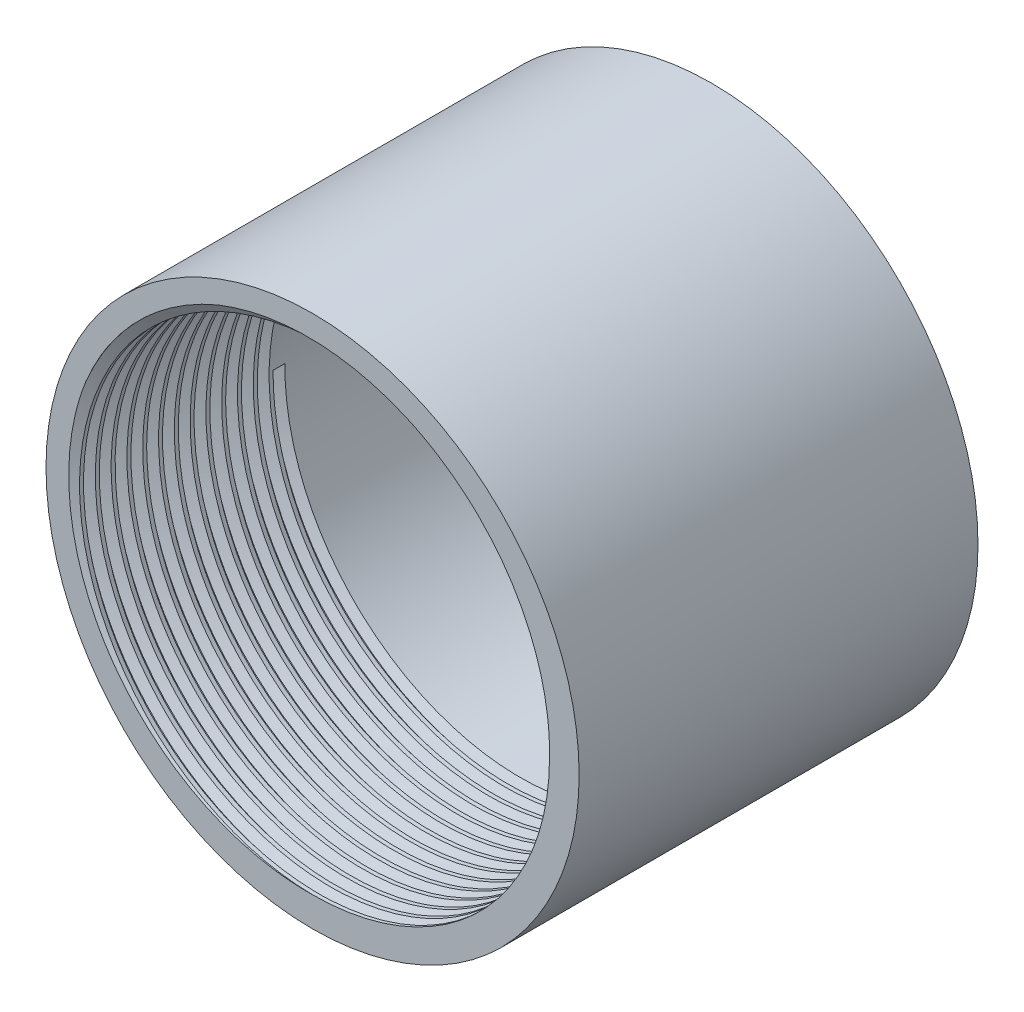
SolidWorks part; units mm, degrees
material "AISI 1035 Acier (SS)"
ref_plane "Plan de face" through (0, 0, 0) normal (0, 0, 1) x (1, 0, 0)
ref_plane "Plan de dessus" through (0, 0, 0) normal (0, 1, 0) x (1, 0, 0)
ref_plane "Plan de droite" through (0, 0, 0) normal (1, 0, 0) x (0, 0, -1)
sketch "Esquisse1" plane through (0, 0, 0) normal (1, 0, 0) x (0, 0, -1)
  line L0 (-10.1, 0) -> (10.1, 0) construction
  line L2 (-10.1, 13.5) -> (10.1, 13.5)
  line L3 (-10.1, 13.5) -> (-10.1, 12)
  line L4 (-10.1, 12) -> (10.1, 12)
  line L5 (10.1, 13.5) -> (10.1, 12)
  dimension "D1" = 20.2
  dimension "D2" = 12
  dimension "D3" = 1.5
revolve "Révolution1" add sketch "Esquisse1" angle 360 about L0
thread "Filetage1" [suppressed] pitch 0.8 start angle 0, offset 2, length 8.5, pitch 0.8, diameter 24
ref_plane "Plan1" through (12, 0, -52.1) normal (0, -1, 0) x (1, 0, 0)
sketch "Profil de filetage1" plane through (12, 0, -52.1) normal (0, -1, 0) x (1, 0, 0)
  line L0 (0, 0) -> (0, 0.8) construction
  line L1 (0, 0) -> (0.433, 0.25)
  line L2 (0.433, 0.25) -> (0.433, 0.35)
  line L3 (0.433, 0.35) -> (0, 0.6)
  line L4 (0.433, 0.3) -> (0, 0.3) construction
  line L11 (0, 0) -> (0, 0.6)
  point P2 (0, 0)
  dimension "Pitch" = 0.8
  dimension "Profile_Angle" = 60
  dimension "Profile_Land" = 0.1
  dimension "Profile_Height" = 0.433
thread "Filetage2" pitch 0.8 method cut profile "Profil de filetage2" start angle 0, offset 2, length 12, pitch 0.8, diameter 24
ref_plane "Plan2" through (-12, 0, 12.1) normal (0, -1, 0) x (-1, 0, 0)
sketch "Profil de filetage2" plane through (-12, 0, 12.1) normal (0, -1, 0) x (-1, 0, 0)
  line L0 (0, 0) -> (0, 0.8) construction
  line L1 (0, 0) -> (0.433, 0.25)
  line L2 (0.433, 0.25) -> (0.433, 0.35)
  line L3 (0.433, 0.35) -> (0, 0.6)
  line L4 (0.433, 0.3) -> (0, 0.3) construction
  line L11 (0, 0) -> (0, 0.6)
  point P2 (0, 0)
  dimension "Pitch" = 0.8
  dimension "Profile_Angle" = 60
  dimension "Profile_Land" = 0.1
  dimension "Profile_Height" = 0.433
sketch "Esquisse4" plane through (0, 0, 0) normal (1, 0, 0) x (0, 0, -1)
  line L1 (-10.1, -13.5) -> (10.1, -13.5)
  line L2 (-10.1, -13.5) -> (-10.1, 13.5)
  line L3 (-10.1, 13.5) -> (10.1, 13.5)
  line L4 (10.1, -13.5) -> (10.1, 13.5)
  line L5 (-10.1, -13.5) -> (10.1, 13.5) construction
  line L6 (-10.1, 13.5) -> (10.1, -13.5) construction
  point P0 (0, 0)
extrude "Enlèv. mat.-Extru.1" [suppressed] cut sketch "Esquisse4" along normal through all
